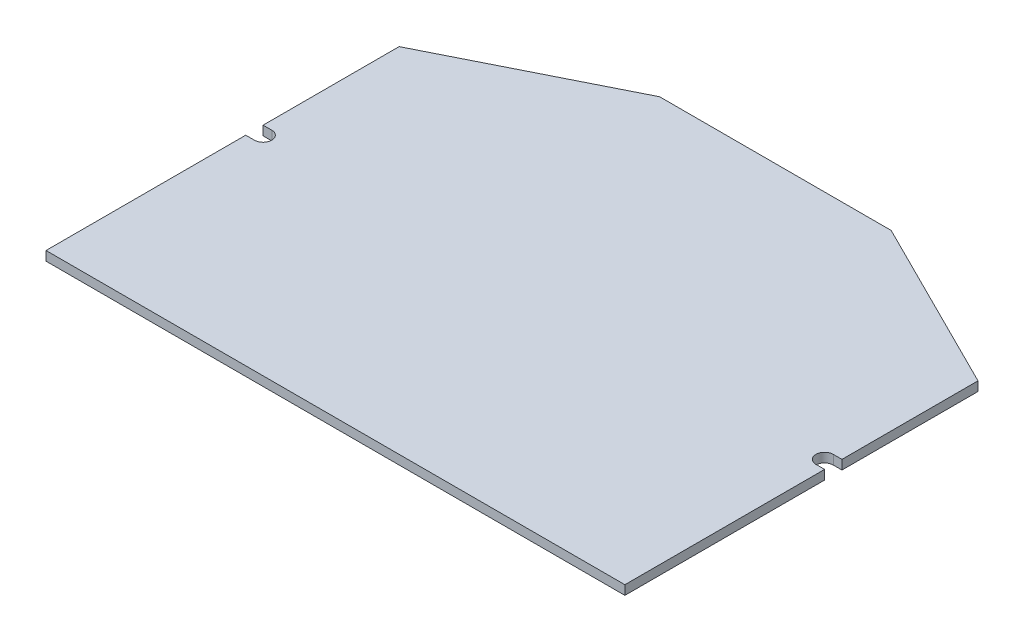
SolidWorks part; units mm, degrees
ref_plane "Front Plane" through (0, 0, 0) normal (0, 0, 1) x (1, 0, 0)
ref_plane "Top Plane" through (0, 0, 0) normal (0, 1, 0) x (1, 0, 0)
ref_plane "Right Plane" through (0, 0, 0) normal (1, 0, 0) x (0, 0, -1)
sketch "Sketch1" plane through (0, 0, 0) normal (0, 1, 0) x (1, 0, 0)
  line L0 (-50, 65) -> (-20, 80)
  line L1 (-50, 4) -> (-50, 38.5)
  line L2 (-50, 65) -> (-50, 41.5)
  line L3 (-20, 80) -> (0, 80)
  line L4 (0, 4) -> (0, 80)
  line L5 (0, 4) -> (-50, 4)
  line L6 (-59.397, 28.2843) -> (-43.8406, 43.8406) construction
  line L7 (-51.9976, -33.7676) -> (-63.9796, -15.3169) construction
  line L8 (-50, 41.5) -> (-48.5, 41.5)
  line L9 (0, 0) -> (-85, 0) construction
  line L10 (-43.8406, 43.8406) -> (0, 0) construction
  line L11 (-51.9976, -33.7676) -> (0, 0) construction
  line L12 (-48.5, 38.5) -> (-50, 38.5)
  circle A0 centre (0, 0) radius 85 construction
  circle A1 centre (-43.8406, 43.8406) radius 1.5 construction
  arc A2 (-48.5, 41.5) -> (-48.5, 38.5) centre (-48.5, 40) cw
  circle A4 centre (-63.9796, -15.3169) radius 1.5 construction
  dimension "D7" = 3
  dimension "D17" = 170
  dimension "D13" = 1.5
  dimension "D2" = 76
  dimension "D3" = 30
  dimension "D4" = 15
  dimension "D5" = 80
  dimension "D6" = 50
  dimension "D8" = 62
  dimension "D9" = 22
  dimension "D10" = 22
  dimension "D11" = 6.1594
  dimension "D12" = 36.1594
  dimension "D14" = 45
  dimension "D15" = 33
  dimension "D16" = 1.5
  dimension "D18" = 40
extrude "Boss-Extrude1" add sketch "Sketch1" along normal blind 1.6
mirror "Mirror1" about plane through (0, 1.6, -4) normal (-1, 0, 0) of "Boss-Extrude1"
